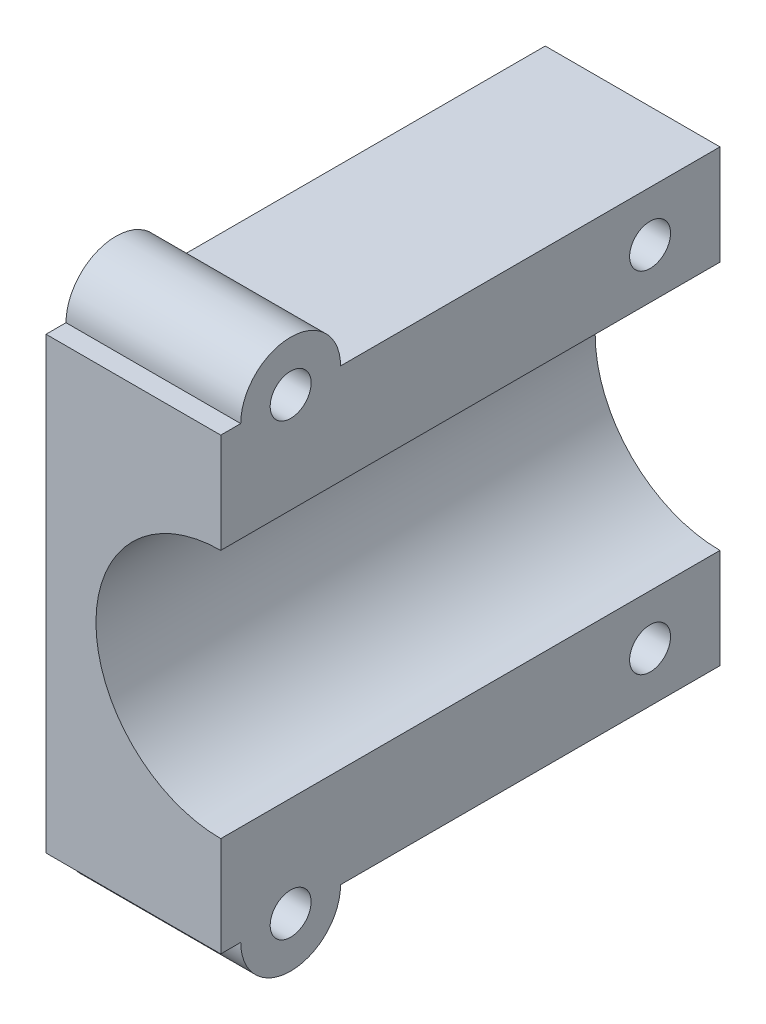
SolidWorks part; units mm, degrees
material "PLA"
ref_plane "Front Plane" through (0, 0, 0) normal (0, 0, 1) x (1, 0, 0)
ref_plane "Top Plane" through (0, 0, 0) normal (0, 1, 0) x (1, 0, 0)
ref_plane "Right Plane" through (0, 0, 0) normal (1, 0, 0) x (0, 0, -1)
sketch "Sketch1" plane through (0, 0, 0) normal (0, 0, 1) x (1, 0, 0)
  line L0 (-17.5, 22.5) -> (-17.5, 0)
  line L1 (55, 0) -> (-55, 0) construction
  line L2 (-17.5, 0) -> (17.5, 0)
  line L3 (17.5, 0) -> (17.5, 22.5)
  line L4 (-17.5, 22.5) -> (-12.5, 22.5)
  line L5 (17.5, 22.5) -> (12.5, 22.5)
  line L6 (0, -44.7868) -> (0, 44.7868) construction
  arc A0 (-12.5, 22.5) -> (12.5, 22.5) centre (0, 22.5) ccw
  dimension "D1" = 12.5
  dimension "D2" = 22.5
  dimension "D3" = 5
extrude "Boss-Extrude1" add sketch "Sketch1" along normal mid plane 50
sketch "Construct1" plane through (0, 0, 0) normal (0, 1, 0) x (1, 0, 0)
  line L0 (17.5, 0) -> (43.4808, -15) construction
  line L1 (-44.2539, 0) -> (44.2539, 0) construction
  line L2 (34.7051, -0.1998) -> (26.2756, -14.8002) construction
  line L3 (17.5, -25) -> (17.5, 25) construction
  point P6 (30.4904, -7.5)
  point P7 (30.4904, -7.5)
  dimension "D1" = 30
  dimension "D2" = 15
ref_plane "LegBuildPlane" through (26.1154, 0, 15.0777) normal (0.866, 0, 0.5) x (0.5, 0, -0.866)
sketch "Sketch5" plane through (26.1154, 0, 15.0777) normal (0.866, 0, 0.5) x (0.5, 0, -0.866)
  line L0 (-8.7, 22.5) -> (-3.75, 22.5)
  line L1 (21.25, 22.5) -> (26.2, 22.5)
  line L2 (17.1795, 0) -> (0.3205, 0) construction
  arc A0 (-3.75, 22.5) -> (21.25, 22.5) centre (8.75, 22.5) ccw
  arc A1 (-8.7, 22.5) -> (26.2, 22.5) centre (8.75, 22.5) ccw
  point P9 (8.75, 0)
  dimension "D1" = 17.45
  dimension "D2" = 12.5
  dimension "D3" = 22.5
  dimension "D4" = 0
extrude "Boss-Extrude2" add sketch "Sketch5" against normal up to surface and the other way blind 30 up to face at (17.5, 11.25, 0)
sketch "Sketch9" plane through (-17.5, 0, 0) normal (-1, 0, 0) x (0, 0, 1)
  line L2 (55, 0) -> (-55, 0) construction
  line L3 (-25, 22.5) -> (-25, 0) construction
  circle A0 centre (-18, 5) radius 2.05
  dimension "D1" = 4.1
  dimension "D2" = 5
  dimension "D3" = 7
extrude "Cut-Extrude3" cut sketch "Sketch9" against normal up to surface (35 mm away) up to face at (17.5, 12.0917, 0)
sketch "Construct2" plane through (0, 22.5, 0) normal (0, 1, 0) x (1, 0, 0)
  line L0 (20.0981, -15.9338) -> (32.5981, 5.7169) construction
  line L2 (50.2211, -33.3253) -> (17.5, -14.4338) construction
  line L3 (62.7211, -11.6747) -> (17.5, 14.4338) construction
  line L4 (17.5, 0) -> (26.3481, -5.1084) construction
  line L11 (-44.2539, 0) -> (44.2539, 0) construction
  dimension "D1" = 3
  dimension "D2" = 90
ref_plane "LegBuildPlane2" through (21.9731, 0, 12.6862) normal (0.866, 0, 0.5) x (0.5, 0, -0.866)
sketch "Sketch12" plane through (21.9731, 0, 12.6862) normal (0.866, 0, 0.5) x (0.5, 0, -0.866)
  line L0 (-3.75, 22.5) -> (21.25, 22.5)
  arc A0 (-3.75, 22.5) -> (21.25, 22.5) centre (8.75, 22.5) ccw
extrude "Boss-Extrude5" add sketch "Sketch12" against normal up to surface (17.4338 mm away) up to face at (17.5, 16.25, 0)
mirror "Mirror1" about plane through (17.5, 22.5, 25) normal (0, -1, 0) of "Boss-Extrude2", "Boss-Extrude1", "Cut-Extrude3", "Boss-Extrude5"
sketch "Sketch13" plane through (0, 0, 0) normal (0, 1, 0) x (1, 0, 0)
  line L0 (17.5, 0) -> (43.4808, -15) construction
  line L1 (47.7461, -37.6121) -> (65.1961, -7.3879) construction
  circle A0 centre (43.4808, -15) radius 1.55
  dimension "D2" = 3.1
  dimension "D1" = 15
extrude "Cut-Extrude4" cut sketch "Sketch13" along normal through all
sketch "Sketch16" plane through (0, 0, 0) normal (1, 0, 0) x (0, 0, -1)
  line L1 (25, 45) -> (-38, 45)
  line L2 (25, 45) -> (25, 0)
  line L3 (25, 0) -> (-38, 0)
  line L4 (-38, 45) -> (-38, 0)
  line L7 (55, 0) -> (-55, 0) construction
  line L8 (0, 44.2539) -> (0, -44.2539) construction
  dimension "D1" = 38
extrude "Cut-Extrude5" cut sketch "Sketch16" along normal up to surface (83.8953 mm away) up to face at (65.1961, 22.5, 7.3879)
sketch "Sketch17" plane through (-17.5, 0, 0) normal (-1, 0, 0) x (0, 0, 1)
  line L0 (55, 0) -> (-55, 0) construction
  line L1 (13, 0) -> (23, 0)
  arc A0 (13, 0) -> (23, 0) centre (18, 0) ccw
  circle A1 centre (-18, 5) radius 2.05 construction
  dimension "D2" = 5
  dimension "D1" = 36
extrude "Boss-Extrude6" add sketch "Sketch17" against normal blind 17.5
sketch "Sketch18" plane through (-17.5, 0, 0) normal (-1, 0, 0) x (0, 0, 1)
  circle A0 centre (18, 0) radius 2.05
  dimension "D1" = 4.1
extrude "Cut-Extrude6" cut sketch "Sketch18" against normal up to surface (17.5 mm away) up to face at (0, 5, -15.95)
ref_plane "HolePlane" through (0, 22.5, 0) normal (0, 1, 0) x (1, 0, 0)
mirror "Mirror2" about plane through (0, 22.5, 0) normal (0, 1, 0) of "Boss-Extrude6", "Cut-Extrude6"
sketch "Sketch20" plane through (0, 0, 0) normal (1, 0, 0) x (0, 0, -1)
  line L0 (-25, 10) -> (25, 10) construction
  line L1 (22.1569, 40) -> (20.0785, 43.6)
  line L2 (20.0785, 43.6) -> (15.9215, 43.6)
  line L3 (15.9215, 43.6) -> (13.8431, 40)
  line L4 (13.8431, 40) -> (15.9215, 36.4)
  line L5 (15.9215, 36.4) -> (20.0785, 36.4)
  line L6 (20.0785, 36.4) -> (22.1569, 40)
  line L7 (-13.8431, 0) -> (-15.9215, 3.6)
  line L8 (-15.9215, 3.6) -> (-20.0785, 3.6)
  line L9 (-20.0785, 3.6) -> (-22.1569, 0)
  line L10 (-22.1569, 0) -> (-20.0785, -3.6)
  line L11 (-20.0785, -3.6) -> (-15.9215, -3.6)
  line L12 (-15.9215, -3.6) -> (-13.8431, 0)
  line L13 (25, 35) -> (-25, 35) construction
  circle A0 centre (18, 40) radius 3.6 construction
  circle A1 centre (-18, 0) radius 3.6 construction
  dimension "D1" = 7.2
extrude "Cut-Extrude7" cut sketch "Sketch20" against normal blind 3.3 from offset 7.35 offset against normal yes
equation "\"TubeDiam\"= 12.5"
equation "\"D1@Sketch1\"=\"TubeDiam\""
equation "\"D2@Sketch1\"=\"ClampHeight\""
equation "\"MountLength\"= 50"
equation "\"D1@Boss-Extrude1\"=\"MountLength\""
equation "\"MountHoleSize\"=3.1"
equation "\"LipWidth\"= 5"
equation "\"D3@Sketch1\"=\"LipWidth\""
equation "\"LegDiam\"= 12.5"
equation "\"LegThickness\"= \"TubeDiam\" + 4.95"
equation "\"D1@Sketch5\"=\"LegThickness\""
equation "\"D2@Sketch5\"=\"TubeDiam\""
equation "\"ClampHeight\"= \"TubeDiam\" + 10"
equation "\"D3@Sketch5\"=\"ClampHeight\""
equation "\"HubHoleDist\"=7"
equation "\"HubHoleSize\"=4.1"
equation "\"D2@Sketch13\"=\"MountHoleSize\""
equation "\"D1@Sketch9\"=\"HubHoleSize\""
equation "\"D3@Sketch9\"=\"HubHoleDist\""
equation "\"D1@Sketch17\"=\"MountLength\" - 2 * \"HubHoleDist\""
equation "\"D1@Boss-Extrude6\"=\"TubeDiam\"+5"
equation "\"D1@Sketch18\"=\"HubHoleSize\""
equation "\"NutInDiam\"=7.2"
equation "\"D1@Sketch20\"=\"NutInDiam\""
